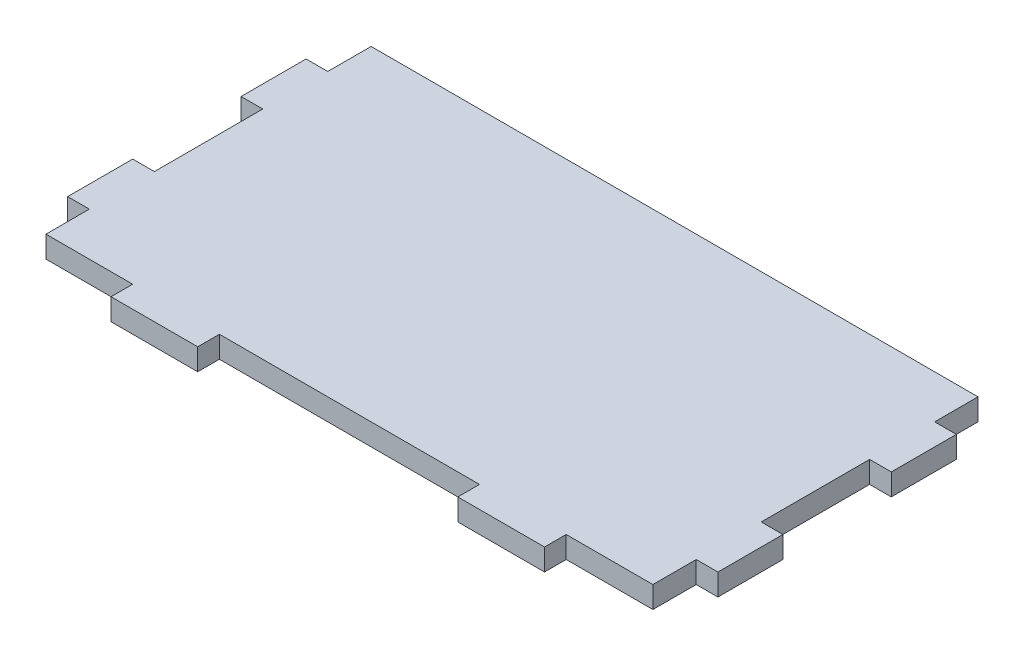
SolidWorks part; units mm, degrees
material "Very Low Density PE (SS)"
ref_plane "Front Plane" through (0, 0, 0) normal (0, 0, 1) x (1, 0, 0)
ref_plane "Top Plane" through (0, 0, 0) normal (0, 1, 0) x (1, 0, 0)
ref_plane "Right Plane" through (0, 0, 0) normal (1, 0, 0) x (0, 0, -1)
sketch "Sketch1" plane through (0, 0, 0) normal (0, 1, 0) x (1, 0, 0)
  line L0 (0, 37.5) -> (0, -37.5) construction
  line L1 (-70, 37.5) -> (-50, 37.5)
  line L2 (-70, 37.5) -> (-70, 27.5)
  line L3 (-70, -37.5) -> (-50, -37.5)
  line L4 (70, 37.5) -> (70, 27.5)
  line L5 (-70, 37.5) -> (70, -37.5) construction
  line L6 (-70, -37.5) -> (70, 37.5) construction
  line L7 (-50, 37.5) -> (-30, 37.5)
  line L13 (50, 37.5) -> (30, 37.5)
  line L15 (-50, 37.5) -> (-30, 37.5) construction
  line L16 (-30, 37.5) -> (30, 37.5)
  line L17 (30, 37.5) -> (50, 37.5) construction
  line L18 (50, 37.5) -> (70, 37.5)
  line L23 (-70, 12.5) -> (-70, -12.5)
  line L24 (-70, 0) -> (70, 0) construction
  line L25 (70, -12.5) -> (75, -12.5)
  line L26 (70, 12.5) -> (70, -12.5)
  line L29 (-70, 12.5) -> (-70, -12.5) construction
  line L30 (-70, -27.5) -> (-70, -37.5)
  line L31 (70, 12.5) -> (70, -12.5) construction
  line L32 (70, -27.5) -> (70, -37.5)
  line L33 (75, -27.5) -> (75, -12.5)
  line L37 (-30, -37.5) -> (-30, -42.5)
  line L38 (-50, -42.5) -> (-30, -42.5)
  line L39 (-50, -37.5) -> (-50, -42.5)
  line L40 (-50, -37.5) -> (-30, -37.5) construction
  line L41 (-30, -37.5) -> (30, -37.5)
  line L42 (30, -37.5) -> (50, -37.5) construction
  line L43 (50, -37.5) -> (70, -37.5)
  line L44 (30, -37.5) -> (30, -42.5)
  line L45 (50, -42.5) -> (30, -42.5)
  line L46 (50, -37.5) -> (50, -42.5)
  line L47 (70, 27.5) -> (75, 27.5)
  line L48 (70, 27.5) -> (70, 12.5) construction
  line L49 (70, 12.5) -> (75, 12.5)
  line L50 (75, 27.5) -> (75, 12.5)
  line L51 (70, -27.5) -> (75, -27.5)
  line L52 (70, -27.5) -> (70, -12.5) construction
  line L53 (-70, -27.5) -> (-70, -12.5) construction
  line L54 (-70, -27.5) -> (-75, -27.5)
  line L55 (-75, -27.5) -> (-75, -12.5)
  line L56 (-70, -12.5) -> (-75, -12.5)
  line L57 (-70, 12.5) -> (-75, 12.5)
  line L58 (-75, 27.5) -> (-75, 12.5)
  line L59 (-70, 27.5) -> (-75, 27.5)
  line L60 (-70, 27.5) -> (-70, 12.5) construction
  line L61 (-70, 27.5) -> (-70, 12.5) construction
  line L62 (-70, -12.5) -> (-70, -27.5) construction
  line L63 (70, -12.5) -> (70, -27.5) construction
  line L64 (70, 27.5) -> (70, 12.5) construction
  point P0 (0, 0)
  dimension "D1" = 140
  dimension "D2" = 75
  dimension "D3" = 20
  dimension "D4" = 5
  dimension "D5" = 20
  dimension "D6" = 5
  dimension "D7" = 10
  dimension "D8" = 15
extrude "Boss-Extrude1" add sketch "Sketch1" along normal blind 5
